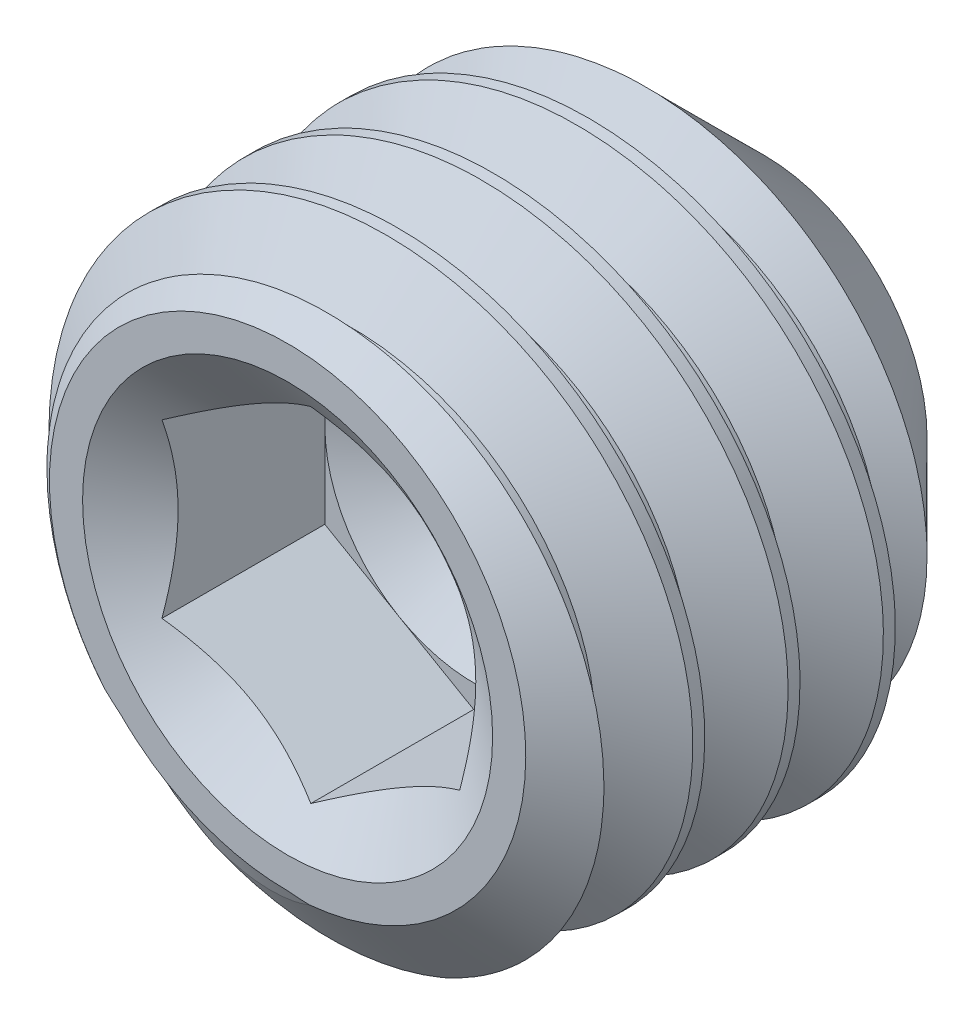
SolidWorks part; units mm, degrees
material "Stainless Steel (ferritic)"
ref_plane "Front" through (0, 0, 0) normal (0, 0, 1) x (1, 0, 0)
ref_plane "Top" through (0, 0, 0) normal (0, 1, 0) x (1, 0, 0)
ref_plane "Right" through (0, 0, 0) normal (1, 0, 0) x (0, 0, -1)
sketch "Sketch1" plane through (0, 0, 0) normal (1, 0, 0) x (0, 0, -1)
  line L0 (-1.5884, 0) -> (-1.5884, 2)
  line L1 (-1.5884, 2) -> (-1.2383, 2.5)
  line L2 (-1.2383, 2.5) -> (1.2815, 2.5)
  line L3 (1.2815, 2.5) -> (2.4116, 1.3699)
  line L4 (2.4116, 1.3699) -> (1.5884, 0)
  line L5 (1.5884, 0) -> (-1.5884, 0)
  line L6 (1.5884, 0) -> (2.4116, 0) construction
  line L7 (2.4116, 0) -> (2.4116, 1.3699) construction
  line L8 (2.4116, -1.3699) -> (1.5884, 0) construction
  line L9 (-1.2383, -2.5) -> (1.2815, -2.5) construction
  line L10 (0, 0) -> (0, -0.8) construction
  point P11 (-1.5884, 2.5)
  point P12 (-3.9685, -2.5)
  point P14 (2.4116, 2.5)
  dimension "Dia" = 5
  dimension "Length" = 4
  dimension "D3" = 35
  dimension "D5" = 118
  dimension "D6" = 45
  dimension "D7" = 4
  dimension "Pitch" = 0.8
  dimension "D1" = 5.25
revolve "Revolve1" add sketch "Sketch1" angle 360 about L6
sketch "Sketch2" plane through (0, 0, 1.5884) normal (0, 0, 1) x (1, 0, 0)
  line L1 (0, 1.4434) -> (-1.25, 0.7217)
  line L2 (-1.25, 0.7217) -> (-1.25, -0.7217)
  line L3 (-1.25, -0.7217) -> (0, -1.4434)
  line L4 (0, -1.4434) -> (1.25, -0.7217)
  line L5 (1.25, -0.7217) -> (1.25, 0.7217)
  line L6 (1.25, 0.7217) -> (0, 1.4434)
  circle A0 centre (0, 0) radius 1.25 construction
  circle A1 centre (0, 0) radius 2.5 construction
  dimension "Hex" = 2.5
extrude "Cut-Extrude1" cut sketch "Sketch2" against normal blind 1.5625
sketch "Sketch3" plane through (0, 0, 1.5884) normal (0, 0, 1) x (1, 0, 0)
  line L0 (0, 1.4434) -> (0, 2) construction
  circle A0 centre (0, 0) radius 1.7217
  point P5 (0, 1.7217)
  dimension "D1" = 0.2783
extrude "Cut-Extrude2" cut sketch "Sketch3" against normal through all draft 55
sketch "Sketch4" plane through (0, 0, 0.0259) normal (0, 0, 1) x (1, 0, 0)
  circle A0 centre (0, 0) radius 1.25 construction
  circle A1 centre (0, 0) radius 1.25
extrude "Cut-Extrude3" cut sketch "Sketch4" against normal through all draft 60
ref_plane "Plane1" through (0, 0, -2.4116) normal (0, 0, 1) x (1, 0, 0)
sketch "Sketch5" plane through (0, 0, -2.4116) normal (0, 0, 1) x (1, 0, 0)
  circle A0 centre (0, 0) radius 2.5 construction
  circle A1 centre (0, 0) radius 2.5
curve "Helix/Spiral1" pitch 0.8 height 4.8 radius 2.5 centre (0, 0, -2.4116) axis (0, 0, 1) start towards (0, 1, 0)
sketch "Sketch6" plane through (0, 0, 0) normal (1, 0, 0) x (0, 0, -1)
  line L0 (2.3616, 2.5866) -> (3.1616, 2.5866) construction
  line L1 (3.1616, 2.5866) -> (2.7616, 1.8938) construction
  line L2 (2.7616, 1.8938) -> (2.3616, 2.5866) construction
  line L3 (2.4116, 2.5) -> (3.1116, 2.5) construction
  line L4 (2.7116, 1.9804) -> (2.8116, 1.9804) construction
  line L5 (2.7616, 2.5) -> (2.7616, 2.5866) construction
  line L7 (2.7616, 1.9804) -> (2.7616, 1.8938) construction
  line L8 (2.7616, 2.5433) -> (2.3866, 2.5433) construction
  line L9 (2.7116, 1.9804) -> (2.3866, 2.5433)
  line L10 (2.3866, 2.5433) -> (3.1366, 2.5433)
  line L11 (3.1366, 2.5433) -> (2.8116, 1.9804)
  line L12 (2.8116, 1.9804) -> (2.7116, 1.9804)
  dimension "D1" = 0.8
  dimension "D2" = 0.1
sweep "Cut-Sweep1" cut profiles "Sketch6" path "Helix/Spiral1"
ref_axis "Center Axis 1" through (0, 0, 2.124) along (0, 0, -1)
ref_plane "Contact Plane 1" through (0, 0, 1.5884) normal (0, 0, 1) x (1, 0, 0)
ref_plane "Contact Plane 2" through (0, 0, -2.4116) normal (0, 0, 1) x (1, 0, 0)
equation "\"D7@Sketch1\" = \"Dia@Sketch1\" * .8"
equation "\"hex Depth@Cut-Extrude1\" = \"Hex@Sketch2\" * .625"
equation "\"D3@Helix/Spiral1\" = \"Length@Sketch1\" + \"Pitch@Sketch1\""
equation "\"D4@Helix/Spiral1\" = \"Pitch@Sketch1\""
equation "\"D1@Sketch6\" = \"Pitch@Sketch1\""
equation "\"D2@Sketch6\"=\"D1@Sketch6\"/8"
